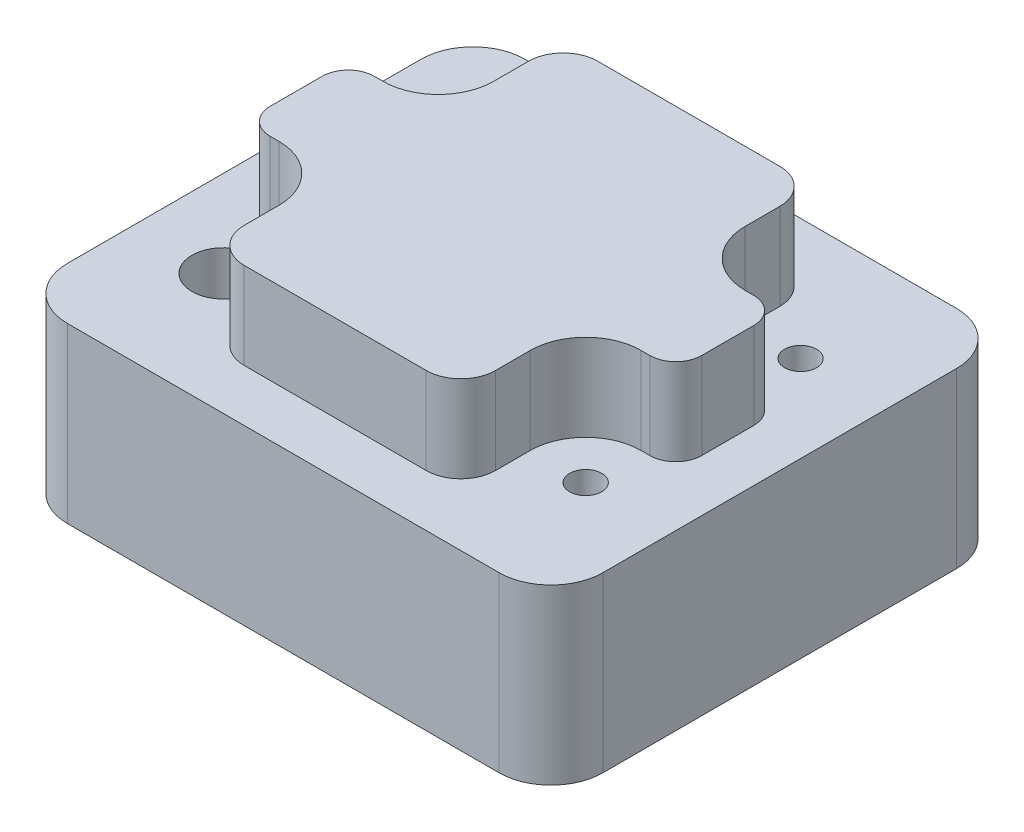
SolidWorks part; units mm, degrees
ref_plane "Front Plane" through (0, 0, 0) normal (0, 0, 1) x (1, 0, 0)
ref_plane "Top Plane" through (0, 0, 0) normal (0, 1, 0) x (1, 0, 0)
ref_plane "Right Plane" through (0, 0, 0) normal (1, 0, 0) x (0, 0, -1)
sketch "Sketch1" plane through (0, 0, 0) normal (0, 1, 0) x (1, 0, 0)
  line L0 (0, 23.7253) -> (0, -0.6764) construction
  line L1 (5.25, 10.2) -> (-5.25, 10.2)
  line L2 (-12.45, 1.5) -> (-12.45, -1.5)
  line L3 (-10.95, 3) -> (-10.45, 3)
  line L4 (-7.25, 8.2) -> (-7.25, 6.2)
  line L13 (-10.45, 6.2) -> (-7.25, 6.2) construction
  line L14 (-10.45, 6.2) -> (-10.45, 3) construction
  line L15 (-14.365, 0) -> (14.365, 0) construction
  line L16 (-10.45, -6.2) -> (-10.45, -3) construction
  line L17 (-10.45, -6.2) -> (-7.25, -6.2) construction
  line L18 (-7.25, -8.2) -> (-7.25, -6.2)
  line L19 (-10.95, -3) -> (-10.45, -3)
  line L20 (10.45, -6.2) -> (7.25, -6.2) construction
  line L21 (10.45, -6.2) -> (10.45, -3) construction
  line L22 (10.45, 6.2) -> (10.45, 3) construction
  line L23 (10.45, 6.2) -> (7.25, 6.2) construction
  line L24 (10.95, -3) -> (10.45, -3)
  line L25 (7.25, -8.2) -> (7.25, -6.2)
  line L26 (7.25, 8.2) -> (7.25, 6.2)
  line L27 (10.95, 3) -> (10.45, 3)
  line L28 (12.45, 1.5) -> (12.45, -1.5)
  line L29 (5.25, -10.2) -> (-5.25, -10.2)
  arc A0 (-10.45, 3) -> (-7.25, 6.2) centre (-10.45, 6.2) ccw
  arc A4 (-7.25, 8.2) -> (-5.25, 10.2) centre (-5.25, 8.2) cw
  arc A10 (-10.95, 3) -> (-12.45, 1.5) centre (-10.95, 1.5) ccw
  arc A11 (-10.95, -3) -> (-12.45, -1.5) centre (-10.95, -1.5) cw
  arc A12 (-7.25, -8.2) -> (-5.25, -10.2) centre (-5.25, -8.2) ccw
  arc A13 (-10.45, -3) -> (-7.25, -6.2) centre (-10.45, -6.2) cw
  arc A14 (10.45, -3) -> (7.25, -6.2) centre (10.45, -6.2) ccw
  arc A15 (7.25, -8.2) -> (5.25, -10.2) centre (5.25, -8.2) cw
  arc A16 (10.95, -3) -> (12.45, -1.5) centre (10.95, -1.5) ccw
  arc A17 (10.95, 3) -> (12.45, 1.5) centre (10.95, 1.5) cw
  arc A18 (7.25, 8.2) -> (5.25, 10.2) centre (5.25, 8.2) ccw
  arc A19 (10.45, 3) -> (7.25, 6.2) centre (10.45, 6.2) cw
  point P1 (0, 0)
  point P9 (0, 0)
  point P11 (0, 0)
  point P13 (5.3, 22.5797)
  point P18 (0, 10.2)
  point P29 (-12.45, 0)
  point P47 (12.45, 0)
  dimension "D2" = 3.2
  dimension "D4" = 2
  dimension "D5" = 6.2
  dimension "D9" = 1.5
  dimension "D1" = 10.45
  dimension "D3" = 12.45
  dimension "D6" = 10.2
  dimension "D7" = 5.25
  dimension "D8" = 2
extrude "Boss-Extrude1" add sketch "Sketch1" along normal blind 5
sketch "Sketch2" plane through (0, 0, 0) normal (0, -1, 0) x (1, 0, 0)
  line L0 (5.25, 10.2) -> (-5.25, 10.2) construction
  line L1 (15.45, -13.2) -> (-15.45, -13.2)
  line L2 (15.45, -13.2) -> (15.45, 13.2)
  line L3 (15.45, 13.2) -> (-15.45, 13.2)
  line L4 (-15.45, -13.2) -> (-15.45, 13.2)
  line L5 (15.45, -13.2) -> (-15.45, 13.2) construction
  line L6 (15.45, 13.2) -> (-15.45, -13.2) construction
  line L7 (-12.45, -1.5) -> (-12.45, 1.5) construction
  point P0 (0, 0)
  dimension "D1" = 3
  dimension "D2" = 3
extrude "Boss-Extrude2" add sketch "Sketch2" along normal blind 10
sketch "Sketch3" plane through (0, -10, 0) normal (0, -1, 0) x (1, 0, 0)
  circle A0 centre (10.45, 6.2) radius 0.925
  circle A1 centre (10.45, -6.2) radius 0.925
  circle A2 centre (-10.45, -6.2) radius 1.815
  circle A3 centre (-10.45, 6.2) radius 1.815
  point P8 (0, 0)
  point P9 (0, 0)
  point P12 (0, 0)
  point P14 (0, 0)
  dimension "D1" = 3.63
  dimension "D2" = 1.85
extrude "Cut-Extrude1" cut sketch "Sketch3" against normal through all
fillet "Fillet1" radius 3 4 edges at (15.45, -5, -13.2) (15.45, -5, 13.2) (-15.45, -5, -13.2) (-15.45, -5, 13.2)
